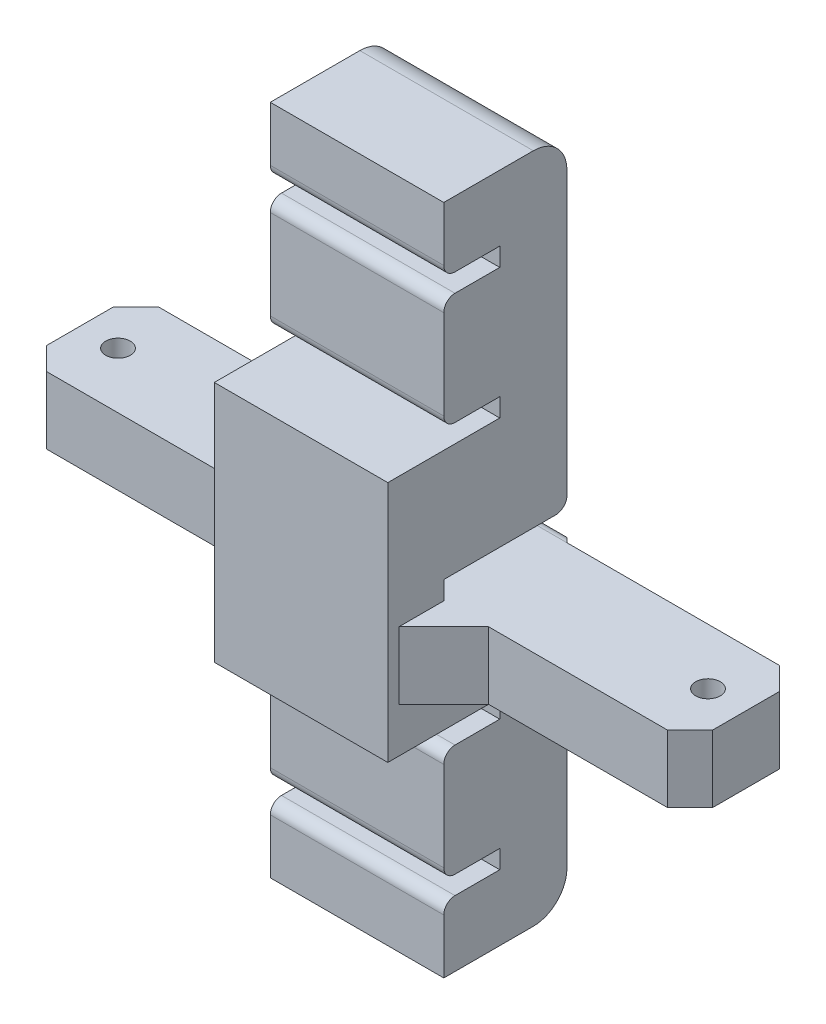
SolidWorks part; units mm, degrees
material "ABS"
ref_plane "Front Plane" through (0, 0, 0) normal (0, 0, 1) x (1, 0, 0)
ref_plane "Top Plane" through (0, 0, 0) normal (0, 1, 0) x (1, 0, 0)
ref_plane "Right Plane" through (0, 0, 0) normal (1, 0, 0) x (0, 0, -1)
sketch "Sketch1" plane through (0, 0, 0) normal (0, 0, 1) x (1, 0, 0)
  line L0 (-7.75, 30) -> (7.75, 30)
  line L1 (-7.75, 30) -> (-7.75, -30)
  line L2 (-7.75, -30) -> (7.75, -30)
  line L3 (7.75, 30) -> (7.75, -30)
  line L4 (-7.75, 30) -> (7.75, -30) construction
  line L5 (-7.75, -30) -> (7.75, 30) construction
  point P0 (0, 0)
  dimension "D1" = 60
  dimension "D2" = 15.5
extrude "Boss-Extrude1" add sketch "Sketch1" along normal blind 8
sketch "Sketch2" plane through (0, 0, 8) normal (0, 0, 1) x (1, 0, 0)
  line L0 (-7.75, 30) -> (-7.75, -30) construction
  line L1 (7.75, -0.825) -> (-7.75, -0.825)
  line L2 (7.75, -0.825) -> (7.75, 0.825)
  line L3 (7.75, 0.825) -> (-7.75, 0.825)
  line L4 (-7.75, -0.825) -> (-7.75, 0.825)
  line L5 (7.75, -0.825) -> (-7.75, 0.825) construction
  line L6 (7.75, 0.825) -> (-7.75, -0.825) construction
  line L7 (-7.75, 5.825) -> (7.75, 5.825) construction
  line L8 (7.75, -30) -> (7.75, 30) construction
  line L9 (7.75, 10.825) -> (-7.75, 12.475) construction
  line L10 (7.75, 12.475) -> (-7.75, 10.825) construction
  line L11 (-7.75, 12.475) -> (-7.75, 10.825)
  line L12 (7.75, 10.825) -> (-7.75, 10.825)
  line L13 (7.75, 12.475) -> (7.75, 10.825)
  line L14 (7.75, 12.475) -> (-7.75, 12.475)
  line L15 (-7.7005, 17.475) -> (7.75, 17.475) construction
  line L16 (7.75, 22.475) -> (-7.75, 24.125) construction
  line L17 (7.75, 24.125) -> (-7.75, 22.475) construction
  line L18 (7.75, 22.475) -> (-7.75, 22.475)
  line L19 (7.75, 22.475) -> (7.75, 24.125)
  line L20 (7.75, 24.125) -> (-7.75, 24.125)
  line L21 (-7.75, 22.475) -> (-7.75, 24.125)
  line L22 (0, 0) -> (20.6292, 0) construction
  line L23 (7.75, -12.475) -> (-7.75, -10.825) construction
  line L24 (7.75, -10.825) -> (-7.75, -12.475) construction
  line L25 (7.75, -12.475) -> (-7.75, -12.475)
  line L26 (7.75, -12.475) -> (7.75, -10.825)
  line L27 (7.75, -10.825) -> (-7.75, -10.825)
  line L28 (-7.75, -12.475) -> (-7.75, -10.825)
  line L29 (7.75, -24.125) -> (-7.75, -22.475) construction
  line L30 (7.75, -22.475) -> (-7.75, -24.125) construction
  line L31 (-7.75, -22.475) -> (-7.75, -24.125)
  line L32 (7.75, -24.125) -> (-7.75, -24.125)
  line L33 (7.75, -22.475) -> (7.75, -24.125)
  line L34 (7.75, -22.475) -> (-7.75, -22.475)
  point P0 (0, 0)
  point P16 (0, 11.65)
  point P23 (0, 23.3)
  point P30 (0, -11.65)
  point P35 (0, -23.3)
  dimension "D1" = 1.65
  dimension "D2" = 10
  dimension "D3" = 10
extrude "Cut-Extrude1" cut sketch "Sketch2" against normal blind 2
sketch "Sketch4" plane through (0, 0, 6) normal (0, 0, 1) x (1, 0, 0)
  line L0 (-7.75, 10.825) -> (-7.75, 0.825) construction
  line L1 (7.75, -0.825) -> (-7.75, -0.825)
  line L2 (7.75, -0.825) -> (7.75, 0.825)
  line L3 (7.75, 0.825) -> (-7.75, 0.825)
  line L4 (-7.75, -0.825) -> (-7.75, 0.825)
  line L5 (7.75, -0.825) -> (-7.75, 0.825) construction
  line L6 (7.75, 0.825) -> (-7.75, -0.825) construction
  line L7 (7.75, 0.825) -> (-7.75, 0.825) construction
  point P0 (0, 0)
extrude "Cut-Extrude2" cut sketch "Sketch4" against normal blind 5
sketch "Sketch5" plane through (7.75, 0, 0) normal (1, 0, 0) x (0, 0, -1)
  line L0 (-8, 10.825) -> (-16, 10.825)
  line L1 (-8, 0.825) -> (-8, 10.825) construction
  line L2 (-16, 10.825) -> (-16, -10.825)
  line L3 (-16, -10.825) -> (-8, -10.825)
  line L4 (-8, -10.825) -> (-8, -0.825) construction
  line L5 (-8, -10.825) -> (-8, -0.825)
  line L6 (-8, -0.825) -> (-11, -0.825)
  line L7 (-43.7, -0.825) -> (-1, -0.825) construction
  line L8 (-11, -0.825) -> (-11, 0.825)
  line L10 (-11, 0.825) -> (-8, 0.825)
  line L11 (-8, 0.825) -> (-8, 10.825)
  line L12 (0, 0) -> (-12.8539, 0) construction
  line L13 (-6, 10.825) -> (-8, 10.825) construction
  dimension "D1" = 3
  dimension "D2" = 8
extrude "Boss-Extrude2" add sketch "Sketch5" against normal up to surface (15.5 mm away) up to face at (-7.75, 0, 6.0833)
sketch "Sketch7" plane through (7.75, 0, 0) normal (1, 0, 0) x (0, 0, -1)
  line L0 (-1, -0.825) -> (-11, -0.825) construction
  line L1 (0, -0.825) -> (-11, -0.825)
  line L2 (0, -0.825) -> (0, 0.825)
  line L3 (0, 0.825) -> (-11, 0.825)
  line L4 (-11, -0.825) -> (-11, 0.825)
  line L5 (0, -0.825) -> (-11, 0.825) construction
  line L6 (0, 0.825) -> (-11, -0.825) construction
  point P0 (-5.5, 0)
extrude "Cut-Extrude3" cut sketch "Sketch7" against normal blind 18
sketch "Sketch8" plane through (0, 0, 8) normal (0, 0, 1) x (1, 0, 0)
  line L4 (7.75, 22.475) -> (-7.75, 22.475)
  line L5 (-7.75, 22.475) -> (-7.75, 12.475)
  line L6 (-7.75, 12.475) -> (7.75, 12.475)
  line L7 (7.75, 12.475) -> (7.75, 22.475)
  line L8 (7.75, 22.475) -> (-7.75, 22.475)
  line L9 (-7.75, 22.475) -> (-7.75, 12.475)
  line L10 (-7.75, 12.475) -> (7.75, 12.475)
  line L11 (7.75, 12.475) -> (7.75, 22.475)
  line L16 (-7.75, 24.125) -> (7.75, 24.125)
  line L17 (7.75, 24.125) -> (7.75, 30)
  line L18 (7.75, 30) -> (-7.75, 30)
  line L19 (-7.75, 30) -> (-7.75, 24.125)
  line L20 (-7.75, -22.475) -> (7.75, -22.475) construction
  line L21 (7.75, -22.475) -> (7.75, -12.475) construction
  line L22 (7.75, -12.475) -> (-7.75, -12.475) construction
  line L23 (-7.75, -12.475) -> (-7.75, -22.475) construction
  line L24 (7.75, -24.125) -> (-7.75, -24.125) construction
  line L25 (-7.75, -24.125) -> (-7.75, -30) construction
  line L26 (-7.75, -30) -> (7.75, -30) construction
  line L27 (7.75, -30) -> (7.75, -24.125) construction
  line L28 (-7.75, 24.125) -> (7.75, 24.125)
  line L29 (7.75, 24.125) -> (7.75, 30)
  line L30 (7.75, 30) -> (-7.75, 30)
  line L31 (-7.75, 30) -> (-7.75, 24.125)
  line L32 (-7.75, -22.475) -> (7.75, -22.475)
  line L33 (7.75, -22.475) -> (7.75, -12.475)
  line L34 (7.75, -12.475) -> (-7.75, -12.475)
  line L35 (-7.75, -12.475) -> (-7.75, -22.475)
  line L36 (7.75, -24.125) -> (-7.75, -24.125)
  line L37 (-7.75, -24.125) -> (-7.75, -30)
  line L38 (-7.75, -30) -> (7.75, -30)
  line L39 (7.75, -30) -> (7.75, -24.125)
  dimension "D1" = 0
  dimension "D2" = 0
extrude "Boss-Extrude3" add sketch "Sketch8" along normal blind 3
fillet "Fillet2" radius 1 8 edges at (0, -24.125, 11) (0, -22.475, 11) (0, -12.475, 11) (0, 12.475, 11) (0, 22.475, 11) (0, 24.125, 11) (0, -0.825, 0) (0, 0.825, 0)
fillet "Fillet3" radius 3 2 edges at (0, -30, 0) (0, 30, 0)
sketch "Sketch9" plane through (7.75, 0, 0) normal (1, 0, 0) x (0, 0, -1)
  line L1 (-1, -6.825) -> (-11, -6.825)
  line L2 (-1, -6.825) -> (-1, -0.825)
  line L3 (-1, -0.825) -> (-11, -0.825)
  line L4 (-11, -6.825) -> (-11, -0.825)
  line L5 (-1, -6.825) -> (-11, -0.825) construction
  line L6 (-1, -0.825) -> (-11, -6.825) construction
  point P0 (-6, -3.825)
  dimension "D1" = 10
  dimension "D2" = 6
extrude "Boss-Extrude4" add sketch "Sketch9" along normal blind 22 and the other way blind 37.5
chamfer "Chamfer2" distance 4 angle 45 2 edges at (7.75, -3.825, 11) (-7.75, -3.825, 11)
sketch "Sketch10" plane through (0, -6.825, 0) normal (0, -1, 0) x (1, 0, 0)
  line L0 (29.75, 11) -> (11.75, 11) construction
  line L1 (29.75, 1) -> (7.75, 1) construction
  line L2 (26.35, 11) -> (26.35, 1) construction
  line L3 (0, 0) -> (0, 18.1508) construction
  circle A0 centre (26.35, 6) radius 1.95
  dimension "D1" = 52.7
  dimension "D2" = 3.9
extrude "Cut-Extrude4" cut sketch "Sketch10" against normal blind 4
hole_wizard "M2 Clearance Hole1" positions "Sketch12" profile "Sketch11" hole size "M2" standard "DIN"
sketch "Sketch12" plane through (0, -6.825, 0) normal (0, -1, 0) x (1, 0, 0)
  point P0 (26.35, 6)
sketch "Sketch11" plane through (26.35, -6.825, 6) normal (1, 0, 0) x (0, 0, -1)
  line L0 (0, 0) -> (0, 10)
  line L1 (0, 10) -> (1.1, 10)
  line L2 (1.1, 10) -> (1.1, 0)
  line L5 (1.1, 0) -> (0, 0)
  line L10 (0, 10) -> (-1.1, 10) construction
  line L11 (0, -6.35) -> (0, 107.95) construction
  dimension "Hole Dia." = 2.2
  dimension "Hole Depth" = 10
  dimension "Drill Angle" = 180
mirror "Mirror4" about plane through (0, 0, 0) normal (1, 0, 0) of "M2 Clearance Hole1", "Cut-Extrude4"
sketch "Sketch13" plane through (0, -6.825, 0) normal (0, -1, 0) x (1, 0, 0)
  line L0 (-29.75, 11) -> (-11.75, 11) construction
  line L1 (-7.75, 2.5) -> (-22.85, 2.5)
  line L2 (-7.75, 2.5) -> (-7.75, 9.5)
  line L3 (-7.75, 9.5) -> (-22.85, 9.5)
  line L4 (-22.85, 2.5) -> (-22.85, 9.5)
  line L5 (-7.75, 2.5) -> (-22.85, 9.5) construction
  line L6 (-7.75, 9.5) -> (-22.85, 2.5) construction
  line L7 (-7.75, 3) -> (-7.75, 0) construction
  line L8 (0, 0) -> (0, 18.1412) construction
  line L9 (7.75, 9.5) -> (22.85, 2.5) construction
  line L10 (7.75, 2.5) -> (22.85, 9.5) construction
  line L11 (22.85, 2.5) -> (22.85, 9.5)
  line L12 (7.75, 9.5) -> (22.85, 9.5)
  line L13 (7.75, 2.5) -> (7.75, 9.5)
  line L14 (7.75, 2.5) -> (22.85, 2.5)
  circle A0 centre (-26.35, 6) radius 1.95 construction
  point P0 (-15.3, 6)
  point P5 (-26.35, 6)
  point P20 (15.3, 6)
  dimension "D1" = 1.5
  dimension "D2" = 3.5
extrude "Cut-Extrude5" cut sketch "Sketch13" against normal blind 5
chamfer "Chamfer3" distance 1 angle 45 2 edges at (7.75, -3.825, 1) (-7.75, -3.825, 1)
chamfer "Chamfer4" distance 2 angle 45 4 edges at (-29.75, -3.825, 1) (-29.75, -3.825, 11) (29.75, -3.825, 1) (29.75, -3.825, 11)
sketch "Sketch15" plane through (-7.75, 0, 0) normal (-1, 0, 0) x (0, 0, 1)
  line L0 (1, 0.825) -> (16, 0.825) construction
  line L1 (2, 2.825) -> (14, 2.825)
  line L2 (14, 2.825) -> (14, 8.825)
  line L3 (14, 8.825) -> (4, 8.825)
  line L4 (4, 8.825) -> (4, 14.475)
  line L5 (4, 14.475) -> (9, 14.475)
  line L6 (9, 14.475) -> (9, 20.475)
  line L7 (9, 20.475) -> (4, 20.475)
  line L8 (4, 20.475) -> (4, 26.125)
  line L9 (4, 26.125) -> (9, 26.125)
  line L10 (9, 26.125) -> (9, 28)
  line L11 (9, 28) -> (3, 28)
  line L12 (2, 27) -> (2, 2.825)
  line L30 (2.5, -6.825) -> (0, -6.825)
  line L31 (0, -6.825) -> (0, -27)
  line L32 (3, -30) -> (11, -30)
  line L33 (11, -30) -> (11, -25.125)
  line L34 (10, -24.125) -> (6, -24.125)
  line L35 (6, -24.125) -> (6, -22.475)
  line L36 (6, -22.475) -> (10, -22.475)
  line L37 (11, -21.475) -> (11, -13.475)
  line L38 (10, -12.475) -> (6, -12.475)
  line L39 (6, -12.475) -> (6, -10.825)
  line L40 (6, -10.825) -> (16, -10.825)
  line L41 (16, -10.825) -> (16, 10.825)
  line L42 (16, 10.825) -> (6, 10.825)
  line L43 (6, 10.825) -> (6, 12.475)
  line L44 (6, 12.475) -> (10, 12.475)
  line L45 (11, 13.475) -> (11, 21.475)
  line L46 (10, 22.475) -> (6, 22.475)
  line L47 (6, 22.475) -> (6, 24.125)
  line L48 (6, 24.125) -> (10, 24.125)
  line L49 (11, 25.125) -> (11, 30)
  line L50 (11, 30) -> (3, 30)
  line L51 (0, 27) -> (0, 1.825)
  line L52 (1, 0.825) -> (11, 0.825)
  line L53 (11, 0.825) -> (11, -0.825)
  line L54 (11, -0.825) -> (15, -0.825)
  line L55 (15, -0.825) -> (15, -6.825)
  line L56 (15, -6.825) -> (9.5, -6.825)
  line L57 (9.5, -6.825) -> (9.5, -1.825)
  line L58 (9.5, -1.825) -> (2.5, -1.825)
  line L59 (2.5, -1.825) -> (2.5, -6.825)
  line L71 (16, 0.825) -> (16, 10.825) construction
  line L72 (16, 10.825) -> (6, 10.825) construction
  line L73 (6, 10.825) -> (6, 12.475) construction
  line L74 (6, 12.475) -> (10, 12.475) construction
  line L75 (11, 13.475) -> (11, 21.475) construction
  line L76 (10, 22.475) -> (6, 22.475) construction
  line L77 (6, 22.475) -> (6, 24.125) construction
  line L78 (6, 24.125) -> (10, 24.125) construction
  line L79 (11, 25.125) -> (11, 30) construction
  line L80 (11, 30) -> (3, 30) construction
  line L81 (0, 27) -> (0, 1.825) construction
  arc A0 (9, 14.475) -> (9, 14.475) centre (9, 14.475) ccw
  arc A1 (9, 20.475) -> (9, 20.475) centre (9, 20.475) ccw
  arc A2 (9, 26.125) -> (9, 26.125) centre (9, 26.125) ccw
  arc A3 (3, 28) -> (2, 27) centre (3, 27) ccw
  arc A4 (2, 2.825) -> (2, 2.825) centre (2, 2.825) ccw
  arc A9 (0, -27) -> (3, -30) centre (3, -27) ccw
  arc A10 (11, -25.125) -> (10, -24.125) centre (10, -25.125) ccw
  arc A11 (10, -22.475) -> (11, -21.475) centre (10, -21.475) ccw
  arc A12 (11, -13.475) -> (10, -12.475) centre (10, -13.475) ccw
  arc A13 (10, 12.475) -> (11, 13.475) centre (10, 13.475) ccw
  arc A14 (11, 21.475) -> (10, 22.475) centre (10, 21.475) ccw
  arc A15 (10, 24.125) -> (11, 25.125) centre (10, 25.125) ccw
  arc A16 (3, 30) -> (0, 27) centre (3, 27) ccw
  arc A17 (0, 1.825) -> (1, 0.825) centre (1, 1.825) ccw
  arc A22 (10, 12.475) -> (11, 13.475) centre (10, 13.475) ccw construction
  arc A23 (11, 21.475) -> (10, 22.475) centre (10, 21.475) ccw construction
  arc A24 (10, 24.125) -> (11, 25.125) centre (10, 25.125) ccw construction
  arc A25 (3, 30) -> (0, 27) centre (3, 27) ccw construction
  arc A26 (0, 1.825) -> (1, 0.825) centre (1, 1.825) ccw construction
  dimension "D1" = 0
  dimension "D2" = 2
extrude "Cut-Extrude7" cut sketch "Sketch15" against normal blind 13
sketch "Sketch16" plane through (-7.75, 0, 0) normal (-1, 0, 0) x (0, 0, 1)
  line L1 (2, -8.825) -> (4, -8.825)
  line L4 (4, -14.475) -> (4, -8.825)
  line L5 (9, -14.475) -> (4, -14.475)
  line L6 (9, -20.475) -> (9, -14.475)
  line L7 (4, -20.475) -> (9, -20.475)
  line L8 (4, -26.125) -> (4, -20.475)
  line L9 (9, -26.125) -> (4, -26.125)
  line L10 (9, -28) -> (9, -26.125)
  line L11 (3, -28) -> (9, -28)
  line L12 (2, -8.825) -> (2, -27)
  line L30 (2.5, -6.825) -> (0, -6.825)
  line L31 (0, -6.825) -> (0, -27)
  line L32 (3, -30) -> (11, -30)
  line L33 (11, -30) -> (11, -25.125)
  line L34 (10, -24.125) -> (6, -24.125)
  line L35 (6, -24.125) -> (6, -22.475)
  line L36 (6, -22.475) -> (10, -22.475)
  line L37 (11, -21.475) -> (11, -13.475)
  line L38 (10, -12.475) -> (6, -12.475)
  line L39 (6, -12.475) -> (6, -10.825)
  line L40 (6, -10.825) -> (16, -10.825)
  line L41 (16, -10.825) -> (16, 10.825)
  line L42 (16, 10.825) -> (6, 10.825)
  line L43 (6, 10.825) -> (6, 12.475)
  line L44 (6, 12.475) -> (10, 12.475)
  line L45 (11, 13.475) -> (11, 21.475)
  line L46 (10, 22.475) -> (6, 22.475)
  line L47 (6, 22.475) -> (6, 24.125)
  line L48 (6, 24.125) -> (10, 24.125)
  line L49 (11, 25.125) -> (11, 30)
  line L50 (11, 30) -> (3, 30)
  line L51 (0, 27) -> (0, 1.825)
  line L52 (1, 0.825) -> (11, 0.825)
  line L53 (11, 0.825) -> (11, -0.825)
  line L54 (11, -0.825) -> (15, -0.825)
  line L55 (15, -0.825) -> (15, -6.825)
  line L56 (15, -6.825) -> (9.5, -6.825)
  line L57 (9.5, -6.825) -> (9.5, -1.825)
  line L58 (9.5, -1.825) -> (2.5, -1.825)
  line L59 (2.5, -1.825) -> (2.5, -6.825)
  line L61 (0, -6.825) -> (0, -27) construction
  line L62 (3, -30) -> (11, -30) construction
  line L63 (11, -30) -> (11, -25.125) construction
  line L64 (10, -24.125) -> (6, -24.125) construction
  line L65 (6, -24.125) -> (6, -22.475) construction
  line L66 (6, -22.475) -> (10, -22.475) construction
  line L67 (11, -21.475) -> (11, -13.475) construction
  line L68 (10, -12.475) -> (6, -12.475) construction
  line L69 (6, -12.475) -> (6, -10.825) construction
  line L90 (2, -8.825) -> (14, -8.825) construction
  line L91 (4, -8.825) -> (14, -8.825) construction
  line L92 (14, -8.825) -> (14, -8.825) construction
  line L93 (0, -6.825) -> (16, -6.825) construction
  line L94 (6, -10.825) -> (16, -10.825) construction
  line L95 (16, -10.825) -> (16, -6.825) construction
  arc A0 (9, -14.475) -> (9, -14.475) centre (9, -14.475) ccw
  arc A1 (9, -20.475) -> (9, -20.475) centre (9, -20.475) ccw
  arc A2 (9, -26.125) -> (9, -26.125) centre (9, -26.125) ccw
  arc A3 (2, -27) -> (3, -28) centre (3, -27) ccw
  arc A9 (0, -27) -> (3, -30) centre (3, -27) ccw
  arc A10 (11, -25.125) -> (10, -24.125) centre (10, -25.125) ccw
  arc A11 (10, -22.475) -> (11, -21.475) centre (10, -21.475) ccw
  arc A12 (11, -13.475) -> (10, -12.475) centre (10, -13.475) ccw
  arc A13 (10, 12.475) -> (11, 13.475) centre (10, 13.475) ccw
  arc A14 (11, 21.475) -> (10, 22.475) centre (10, 21.475) ccw
  arc A15 (10, 24.125) -> (11, 25.125) centre (10, 25.125) ccw
  arc A16 (3, 30) -> (0, 27) centre (3, 27) ccw
  arc A17 (0, 1.825) -> (1, 0.825) centre (1, 1.825) ccw
  arc A18 (0, -27) -> (3, -30) centre (3, -27) ccw construction
  arc A19 (11, -25.125) -> (10, -24.125) centre (10, -25.125) ccw construction
  arc A20 (10, -22.475) -> (11, -21.475) centre (10, -21.475) ccw construction
  arc A21 (11, -13.475) -> (10, -12.475) centre (10, -13.475) ccw construction
  dimension "D1" = 0
  dimension "D2" = 2
extrude "Cut-Extrude8" cut sketch "Sketch16" against normal blind 13
